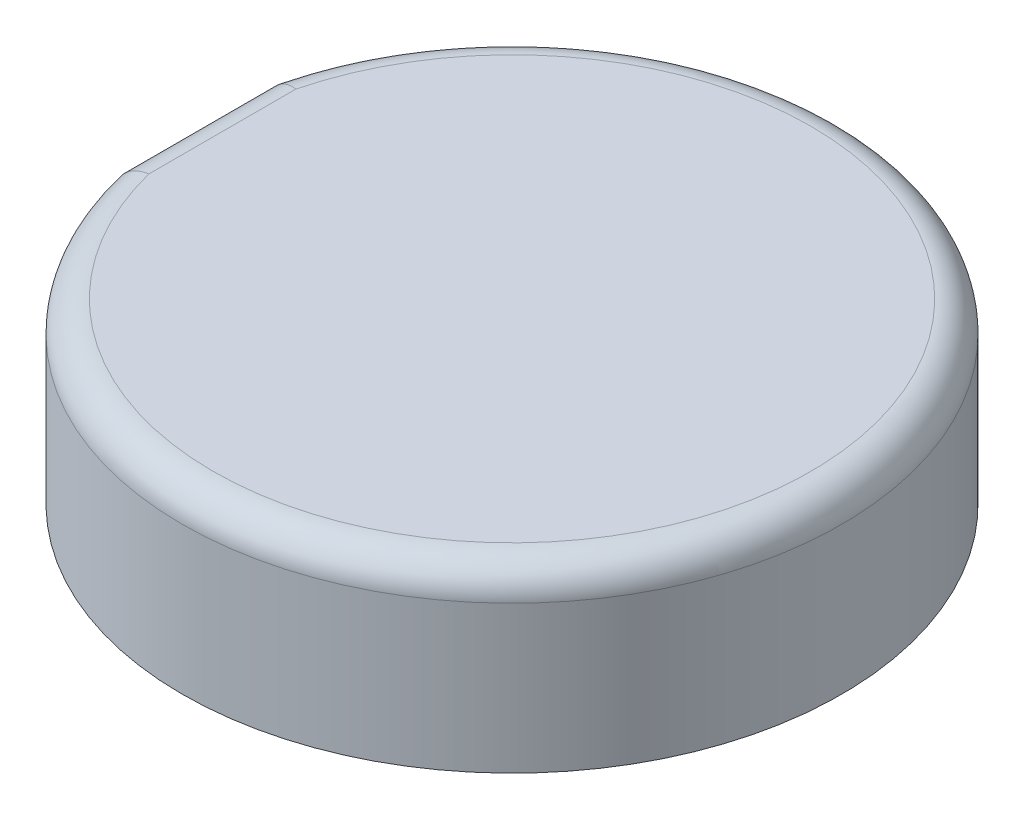
SolidWorks part; units mm, degrees
ref_plane "Plan de face" through (0, 0, 0) normal (0, 0, 1) x (1, 0, 0)
ref_plane "Plan de dessus" through (0, 0, 0) normal (0, 1, 0) x (1, 0, 0)
ref_plane "Plan de droite" through (0, 0, 0) normal (1, 0, 0) x (0, 0, -1)
sketch "Esquisse1" plane through (0, 0, 0) normal (0, 1, 0) x (1, 0, 0)
  line L0 (-10.45, -2.5219) -> (-10.45, 2.5219)
  arc A0 (-10.45, -2.5219) -> (-10.45, 2.5219) centre (0, 0) ccw
  point P1 (-10.45, 0)
  dimension "D1" = 21.5
  dimension "D2" = 10.45
extrude "Boss.-Extru.1" add sketch "Esquisse1" along normal blind 5.8
fillet "Congé1" radius 1 2 edges at (-10.45, 5.8, 0) (10.75, 5.8, 0)
